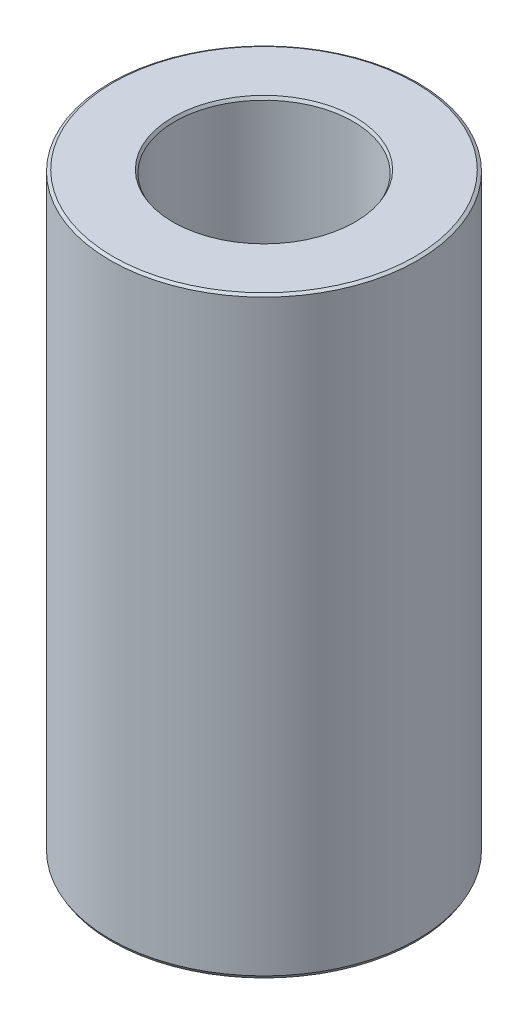
SolidWorks part; units mm, degrees
ref_plane "Front Plane" through (0, 0, 0) normal (0, 0, 1) x (1, 0, 0)
ref_plane "Top Plane" through (0, 0, 0) normal (0, 1, 0) x (1, 0, 0)
ref_plane "Right Plane" through (0, 0, 0) normal (1, 0, 0) x (0, 0, -1)
sketch "Sketch1" plane through (0, 0, 0) normal (0, 1, 0) x (1, 0, 0)
  circle A0 centre (0, 0) radius 57.5
  dimension "SLEEVE_OD" = 115
extrude "Boss-Extrude1" add sketch "Sketch1" along normal blind 221.5071
sketch "Sketch2" plane through (0, 0, 0) normal (0, 1, 0) x (1, 0, 0)
  circle A0 centre (0, 0) radius 33.3644
  dimension "BORE_D" = 66.7288
extrude "Cut-Extrude1" cut sketch "Sketch2" along normal through all
chamfer "Chamfer1" distance 0.6445 angle 60 4 edges at (0, 221.5071, 33.3644) (0, 0, 33.3644) (0, 0, 57.5) (0, 221.5071, 57.5) first distance on face at (0, 221.5071, 33.3644) first distance on face at (0, 0, 33.3644) first distance on face at (0, 221.5071, 57.5)
